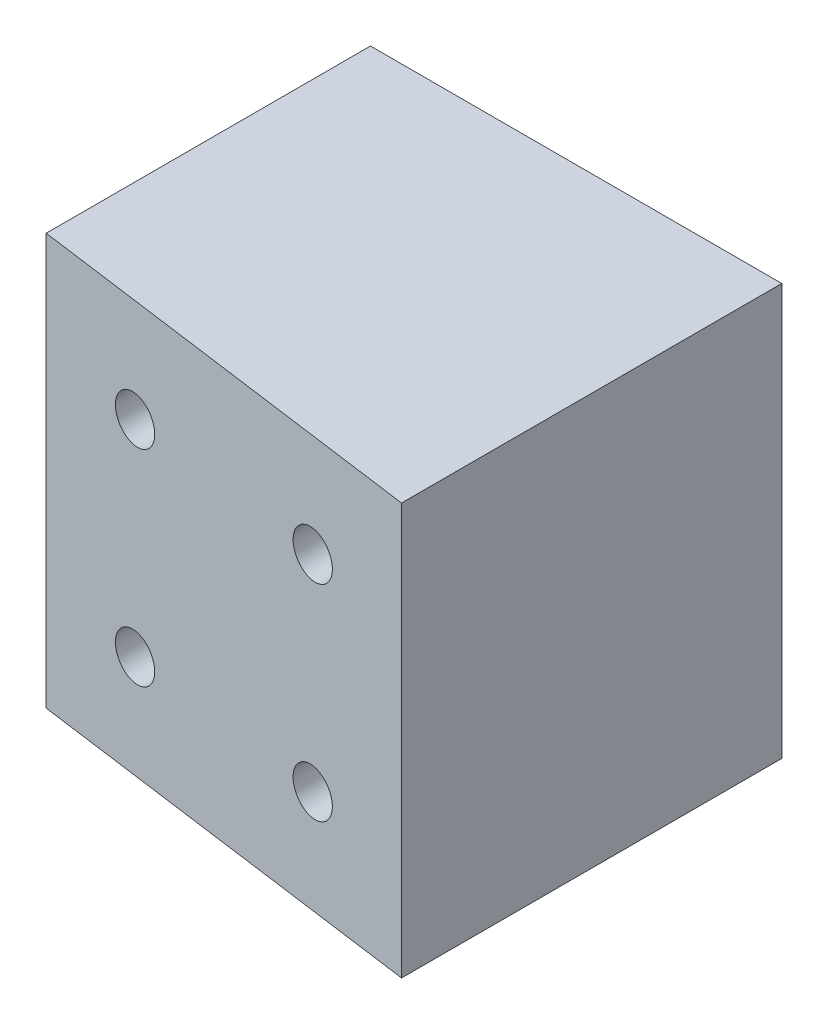
SolidWorks part; units mm, degrees
ref_plane "Front Plane" through (0, 0, 0) normal (0, 0, 1) x (1, 0, 0)
ref_plane "Top Plane" through (0, 0, 0) normal (0, 1, 0) x (1, 0, 0)
ref_plane "Right Plane" through (0, 0, 0) normal (1, 0, 0) x (0, 0, -1)
sketch "Sketch1" plane through (0, 0, 0) normal (0, 1, 0) x (1, 0, 0)
  line L1 (-94.6194, -34.0812) -> (138.1834, -65.7727) construction
  line L2 (0, 0) -> (-50.8, 0)
  line L3 (-50.8, -40.0463) -> (0, -46.9617)
  line L4 (0, 0) -> (0, -46.9617)
  line L5 (0, 0) -> (-12.573, 0) construction
  line L6 (-50.8, 0) -> (-50.8, -40.0463)
  dimension "D1" = 50.8
extrude "Boss-Extrude1" add sketch "Sketch1" along normal blind 50.8
sketch "Sketch3" plane through (0, 0, 0) normal (0, 0, -1) x (-1, 0, 0)
  line L0 (0, 50.8) -> (50.8, 0) construction
  line L3 (0, 0) -> (50.8, 50.8) construction
  line L4 (12.7, 38.1) -> (38.1, 38.1)
  line L5 (12.7, 38.1) -> (12.7, 12.7)
  line L6 (12.7, 12.7) -> (38.1, 12.7)
  line L7 (38.1, 38.1) -> (38.1, 12.7)
  dimension "D1" = 25.4
hole_wizard "CSK for #10 Flat Head Machine Screw (100)2" positions "Sketch6" profile "Sketch7" countersink size "#10" standard "ANSI Inch" end condition through all
sketch "Sketch6" plane through (295.342, -214.7951, 50.8) normal (0, 0, -1) x (-1, 0, 0)
  point P0 (333.442, 227.4951)
  point P2 (333.442, 252.8951)
  point P4 (333.442, 329.0951)
  point P6 (333.442, 354.4951)
sketch "Sketch7" plane through (-38.1, 12.7, 50.8) normal (1, 0, 0) x (0, -1, 0)
  line L0 (0, 0) -> (0, 50.8)
  line L1 (0, 50.8) -> (2.8067, 50.8)
  line L2 (2.8067, 50.8) -> (2.8067, 6.0833)
  line L3 (2.8067, 6.0833) -> (8.89, 0)
  line L4 (8.89, 0) -> (0, 0)
  line L5 (-2.8067, 6.0833) -> (-8.89, 0) construction
  line L6 (0, -6.35) -> (0, 107.95) construction
  dimension "Thru Hole Dia." = 5.6134
  dimension "Thru Hole Depth" = 50.8
  dimension "Near C'Sink Dia." = 17.78
  dimension "Near C'Sink Angle" = 90
hole_wizard "CSK for #10 Flat Head Machine Screw (100)3" positions "Sketch8" profile "Sketch9" countersink size "#10" standard "ANSI Inch" end condition through all
sketch "Sketch8" plane through (295.342, -316.3951, 53.34) normal (0, 0, -1) x (-1, 0, 0)
  point P0 (308.042, 252.8951)
  point P2 (308.042, 227.4951)
  point P4 (308.042, 329.0951)
  point P6 (308.042, 354.4951)
sketch "Sketch9" plane through (-12.7, -63.5, 53.34) normal (1, 0, 0) x (0, -1, 0)
  line L0 (0, 0) -> (0, 53.34)
  line L1 (0, 53.34) -> (2.8067, 53.34)
  line L2 (2.8067, 53.34) -> (2.8067, 6.0833)
  line L3 (2.8067, 6.0833) -> (8.89, 0)
  line L4 (8.89, 0) -> (0, 0)
  line L5 (-2.8067, 6.0833) -> (-8.89, 0) construction
  line L6 (0, -6.35) -> (0, 107.95) construction
  dimension "Thru Hole Dia." = 5.6134
  dimension "Thru Hole Depth" = 53.34
  dimension "Near C'Sink Dia." = 17.78
  dimension "Near C'Sink Angle" = 90
